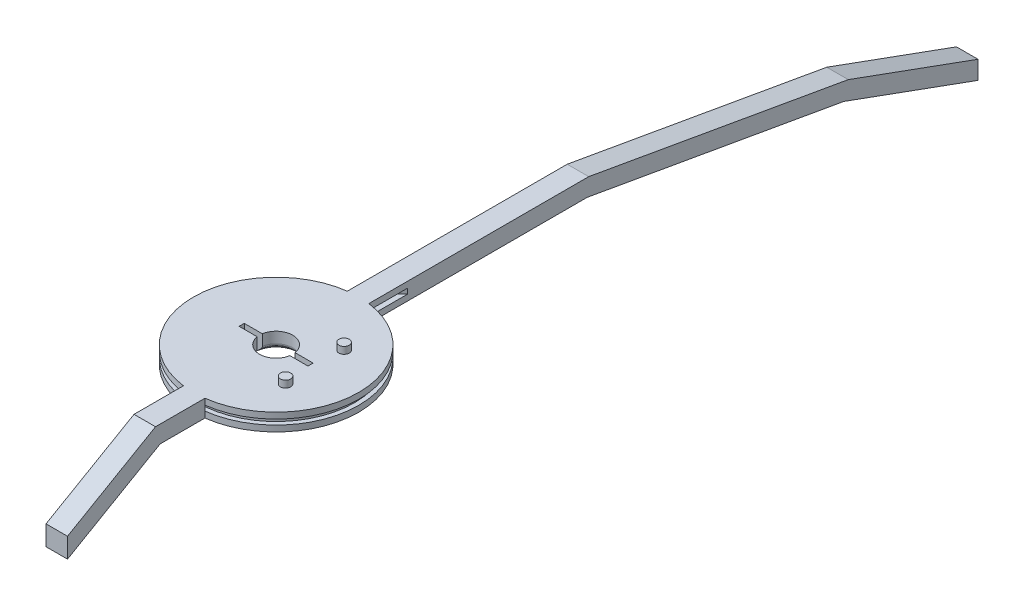
SolidWorks part; units mm, degrees
ref_plane "Front Plane" through (0, 0, 0) normal (0, 0, 1) x (1, 0, 0)
ref_plane "Top Plane" through (0, 0, 0) normal (0, 1, 0) x (1, 0, 0)
ref_plane "Right Plane" through (0, 0, 0) normal (1, 0, 0) x (0, 0, -1)
sketch "Sketch1" plane through (0, 0, 0) normal (0, 1, 0) x (1, 0, 0)
  circle A0 centre (0, 0) radius 9.1071
  dimension "D1" = 18.2143
extrude "MidSection" add sketch "Sketch1" along normal blind 0.6
ref_plane "Plane1" through (0, 0.3, 0) normal (0, 1, 0) x (1, 0, 0)
sketch "Sketch2" plane through (0, 0, 0) normal (1, 0, 0) x (0, 0, -1)
  line L0 (9.1071, 0.6) -> (-9.1071, 0.6) construction
  line L1 (9.1071, 0.6) -> (-9.1071, 0.6)
  line L2 (0, 0.6) -> (0, 1.3)
  line L3 (0, 1.3) -> (9.6071, 1.3)
  line L4 (9.6071, 1.3) -> (9.6071, 1)
  line L5 (9.6071, 1) -> (9.1071, 0.6)
  line L6 (0, 0.6) -> (0, 3.326) construction
  line L7 (9.1071, 0.6) -> (9.6071, 0.6)
  line L8 (9.6071, 0.6) -> (9.6071, 1)
  dimension "D1" = 0.7
  dimension "D2" = 0.5
  dimension "D3" = 0.3
revolve "Cap" add sketch "Sketch2" angle 360 about L6 region at (0, 0.9533, -4.7336) region at (0, 0.7333, -9.4405)
mirror "Cap2" about plane through (0, 0.3, 0) normal (0, 1, 0) of "Cap"
ref_plane "Plane2" through (9.1071, 0, 0) normal (1, 0, 0) x (0, 0, -1)
sketch "Sketch5" plane through (0, 1.3, 0) normal (0, 1, 0) x (1, 0, 0)
  line L3 (-8.4077, 3.5) -> (8.4077, 3.5) construction
  line L9 (0, 0) -> (-3.1386, 0) construction
  line L11 (-8.5633, 3.1) -> (8.4077, 3.1)
  line L15 (-8.2298, 3.9) -> (8.2298, 3.9)
  line L16 (-8.4077, 3.9) -> (8.4077, 3.9) construction
  line L17 (-8.4077, 3.1) -> (8.4077, 3.1) construction
  line L18 (8.4077, 3.1) -> (8.5633, 3.1)
  line L19 (8.4077, -3.1) -> (8.5633, -3.1)
  line L20 (-8.2298, -3.9) -> (8.2298, -3.9)
  line L21 (-8.5633, -3.1) -> (8.4077, -3.1)
  line L22 (-5.919, 3.1) -> (-5.919, 3.9)
  line L23 (-5.919, -3.1) -> (-5.919, -3.9)
  arc A2 (-5.919, 3.1) -> (-9.1049, 0.2) centre (-5.919, -0.1) ccw
  circle A3 centre (0, 0) radius 9.1071 construction
  arc A8 (-5.919, -3.1) -> (-9.1049, -0.2) centre (-5.919, 0.1) cw
  circle A14 centre (0, 0) radius 9.1071
  dimension "D1" = 3.2
  dimension "D4" = 0.4
  dimension "D2" = 0.2
  dimension "D3" = 3.5
  dimension "D5" = 0.4
extrude "CableSlots" cut sketch "Sketch5" against normal up to surface (1.3 mm away) from surface contours L15 A14 L11 L22 | L11 A14 A2 | A8 A14 L21 | L21 A14 L20 L23 region at (-7.1634, 1.3, -3.4911) region at (-8.2017, 1.3, -2.422) region at (-8.2017, 1.3, 2.422) region at (-7.1634, 1.3, 3.4911) up to face at (0, 0, 9.1071) starting at face at (0, 0.6, 9.1071)
sketch "Sketch6" plane through (0, 1.3, 0) normal (0, 1, 0) x (1, 0, 0)
  line L0 (-5.919, -3.1) -> (-5.919, -3.9) construction
  line L1 (-5.919, -3.1) -> (-5.919, -3.9) construction
  line L2 (0, 0) -> (2.8045, 0) construction
  circle A0 centre (4.5, -3.4) radius 1
  circle A1 centre (4.5, 3.4) radius 1
  circle A2 centre (4.5, 3.4) radius 0.6
  circle A13 centre (4.5, -3.4) radius 0.6
  dimension "D4" = 1.2
  dimension "D2" = 4.5
extrude "CablePresserBolt_Markers" add sketch "Sketch6" along normal offset from surface (0.8 mm away) 0.8 contours A2 | A13 region at (4.5, 1.3, -3.4) region at (4.5, 1.3, 3.4) up to face at (0, 1.3, -9.6071) offset beyond the face yes
sketch "Sketch8" plane through (0, 1.3, 0) normal (0, 1, 0) x (1, 0, 0)
  circle A0 centre (0, 0) radius 1.925
  dimension "D1" = 3.85
extrude "BallBearingSlot" cut sketch "Sketch8" against normal through all
sketch "Sketch15" plane through (0, 0, 0) normal (1, 0, 0) x (0, 0, -1)
  line L0 (-9.6071, -0.7) -> (9.6071, -0.7) construction
  line L1 (-9.6071, -0.7) -> (9.6071, -0.7) construction
  line L2 (0, -0.7) -> (2.5, -0.7)
  line L3 (1.925, 0.0307) -> (1.925, 1.8136) construction
  line L4 (2.5, -0.7) -> (2.1, -0.3)
  line L5 (1.925, 0.0307) -> (1.925, -0.7)
  arc A0 (1.925, 0.0307) -> (2.1, -0.3) centre (2.325, 0.0307) ccw
  dimension "D5" = 0.4
  dimension "D1" = 2.5
  dimension "D2" = 1.925
  dimension "D4" = 0.4
  dimension "D3" = 2.1
revolve "BearingInsertionSlope" cut sketch "Sketch15" angle 360 about axis through (0, 0.6, 0) along (0, -1, 0) region at (0, -0.5032, -2.1143)
sketch "Sketch16" plane through (0, -0.7, 0) normal (0, -1, 0) x (1, 0, 0)
  line L0 (0, 0) -> (4, 0) construction
  line L1 (0, -0.3) -> (4, -0.3)
  line L2 (0, 0.3) -> (4, 0.3)
  line L3 (0, -0.3) -> (0, 0.3)
  line L4 (4, -0.3) -> (4, 0.3)
  dimension "D1" = 4
  dimension "D2" = 0.3
  dimension "D3" = 0.3
extrude "DeformCut" cut sketch "Sketch16" against normal through all
pattern_circular "CirPattern1" count 2 over 360 about axis through (0, 1.3, 0) along (0, 1, 0) of "DeformCut"
sketch "Sketch17" plane through (0, 0, 0) normal (1, 0, 0) x (0, 0, -1)
  line L0 (0, 0.3) -> (35, 0.3) construction
  line L1 (35, 0.3) -> (65, -4.9898) construction
  line L2 (65, -4.9898) -> (80, -10.4494) construction
  line L3 (0, 0.3) -> (-15, 0.3) construction
  line L4 (-15, 0.3) -> (-25, -5.4735) construction
  line L5 (0, 1.3) -> (0, -0.7) construction
  line L6 (65.2598, -4.0202) -> (80.342, -9.5097)
  line L7 (35.0875, 1.3) -> (65.2598, -4.0202)
  line L8 (0, 1.3) -> (35.0875, 1.3)
  line L9 (0.3, -0.7) -> (0.3, 1.3)
  line L10 (-0.3, -0.7) -> (0.3, -0.7)
  line L11 (-0.3, 1.3) -> (-0.3, -0.7)
  line L12 (0.3, 1.3) -> (-0.3, 1.3)
  line L13 (0.3, -0.7) -> (0.3, 1.3) construction
  line L14 (-0.3, -0.7) -> (0.3, -0.7) construction
  line L15 (-0.3, 1.3) -> (-0.3, -0.7) construction
  line L16 (0.3, 1.3) -> (-0.3, 1.3) construction
  line L17 (0, 1.3) -> (-15.2679, 1.3)
  line L18 (-15.2679, 1.3) -> (-25.5, -4.6075)
  line L19 (64.7402, -5.9594) -> (79.658, -11.3891)
  line L20 (34.9125, -0.7) -> (64.7402, -5.9594)
  line L21 (0, -0.7) -> (34.9125, -0.7)
  line L22 (0, -0.7) -> (-14.7321, -0.7)
  line L23 (-14.7321, -0.7) -> (-24.5, -6.3395)
  line L24 (-25.5, -4.6075) -> (-25.5, -6.9169)
  line L25 (-25.5, -6.9169) -> (-24.5, -6.3395)
  line L28 (80.342, -9.5097) -> (80.342, -11.638)
  line L29 (80.342, -11.638) -> (79.658, -11.3891)
  line L30 (-9.6071, 1.3) -> (-9.6071, 0.6) construction
  line L31 (-9.6071, 1.3) -> (-9.6071, 0.6)
  line L32 (9.6071, 0.6) -> (9.6071, 1.3) construction
  line L33 (9.6071, 0.6) -> (9.6071, 1.3)
  line L34 (-9.6071, 0.6) -> (-9.6071, -0.7)
  line L35 (-9.6071, 0) -> (-9.6071, -0.7) construction
  line L36 (9.6071, 0.6) -> (9.6071, -0.7)
  line L37 (9.6071, -0.7) -> (9.6071, 0) construction
  dimension "D1" = 170
  dimension "D2" = 170
  dimension "D3" = 80
  dimension "D4" = 35
  dimension "D5" = 30
  dimension "D6" = 150
  dimension "D7" = 25
  dimension "D8" = 15
  dimension "D9" = 0
  dimension "D10" = 1
  dimension "D11" = 1
extrude "BossExtrude" add sketch "Sketch17" along normal mid plane 2.5 separate body contours L34 L31 L17 L18 L24 L25 L23 L22 | L33 L36 L21 L20 L19 L29 L28 L6 L7 L8 region at (0, -7.4406, -72.555) region at (0, -1.7992, 17.8035)
sketch "Sketch18" plane through (0, 0, -9.6071) normal (0, 0, 1) x (1, 0, 0)
  line L4 (-1.25, 1.3) -> (-1.25, -0.7)
  line L5 (-1.25, -0.7) -> (1.25, -0.7)
  line L6 (1.25, -0.7) -> (1.25, 1.3)
  line L7 (1.25, 1.3) -> (-1.25, 1.3)
  line L8 (-1.25, 1.3) -> (-1.25, -0.7)
  line L9 (-1.25, -0.7) -> (1.25, -0.7)
  line L10 (1.25, -0.7) -> (1.25, 1.3)
  line L11 (1.25, 1.3) -> (-1.25, 1.3)
  dimension "D1" = 0
extrude "Boss-Extrude3" add sketch "Sketch18" along normal up to surface (0.0817 mm away) up to face at (0, 0.6, -9.6071)
sketch "Sketch19" plane through (0, 0, 9.6071) normal (0, 0, -1) x (-1, 0, 0)
  line L4 (1.25, -0.7) -> (1.25, 1.3)
  line L5 (1.25, 1.3) -> (-1.25, 1.3)
  line L6 (-1.25, 1.3) -> (-1.25, -0.7)
  line L7 (-1.25, -0.7) -> (1.25, -0.7)
  line L8 (1.25, -0.7) -> (1.25, 1.3)
  line L9 (1.25, 1.3) -> (-1.25, 1.3)
  line L10 (-1.25, 1.3) -> (-1.25, -0.7)
  line L11 (-1.25, -0.7) -> (1.25, -0.7)
  dimension "D1" = 0
extrude "Boss-Extrude4" add sketch "Sketch19" along normal up to surface (0.0817 mm away) up to face at (0, 0.95, 0.0408)
sketch "Sketch14" plane through (0, 1.3, 0) normal (0, 1, 0) x (1, 0, 0)
  line L2 (-6.4072, 6.4721) -> (1.25, 14.0255)
  line L3 (-1.25, 9.5255) -> (-1.25, 35.0875) construction
  line L4 (1.25, 9.5255) -> (1.25, 35.0875) construction
  line L5 (-1.25, 9.5255) -> (-1.25, 35.0875)
  line L6 (1.25, 9.5255) -> (1.25, 35.0875)
  arc A2 (-8.2298, -3.9) -> (-8.2298, 3.9) centre (0, 0) ccw construction
  arc A3 (-8.2298, -3.9) -> (-8.2298, 3.9) centre (0, 0) ccw construction
  arc A8 (1.25, 9.5255) -> (-1.25, 9.5255) centre (0, 0) ccw
  arc A9 (-1.25, 9.5255) -> (-1.25, -9.5255) centre (0, 0) ccw
  arc A10 (-1.25, -9.5255) -> (1.25, -9.5255) centre (0, 0) ccw
  arc A11 (1.25, -9.5255) -> (1.25, 9.5255) centre (0, 0) ccw
  arc A12 (1.25, 9.5255) -> (-1.25, 9.5255) centre (0, 0) ccw
  arc A13 (-1.25, 9.5255) -> (-1.25, -9.5255) centre (0, 0) ccw
  arc A14 (-1.25, -9.5255) -> (1.25, -9.5255) centre (0, 0) ccw
  arc A15 (1.25, -9.5255) -> (1.25, 9.5255) centre (0, 0) ccw
  line M41 (1.25, 9.5255) -> (1.25, 35.0875)
  line M43 (-1.25, 35.0875) -> (-1.25, 9.5255)
  dimension "D1" = 4.5
  dimension "D2" = 0
extrude "CableClearanceCut" cut sketch "Sketch14" against normal up to surface (1.3 mm away) from surface contours A12 L2 M41 M43 region at (0.1599, 1.3, -11.265) up to face at (-5.2666, 0, 0) starting at face at (-5.2666, 0.6, 0)
equation "\"BoltD\"=2mm"
equation "\"SmallScrewD\"=1.2mm"
equation "\"SmallScrewHatD\"=2mm"
equation "\"TubeOuterD\"=1.2mm"
equation "\"BasicPulleyD\"=15mm"
equation "\"GrooveDepth\"=0.7mm"
equation "\"Cable1D\"=0.4mm"
equation "\"Cable2D\"=0.3mm"
equation "\"BallBearingInnerD\"=2mm"
equation "\"BallBearingOuterD\"=4mm"
equation "\"D1@Sketch1\" = \"PulleyD\""
equation "\"D1@MidSection\"=\"Cable2D\" * 2"
equation "\"D4@Sketch6\"=\"SmallScrewD\""
equation "\"D1@Sketch8\"=\"BallBearingOuterD\"-0.15"
equation "\"BoltHatD\"=3.2mm"
equation "\"BallBearingThickness\"=2mm"
equation "\"HumerusL\"=37.2mm"
equation "\"HumerusElbowSidePulleyD\"=10mm"
equation "\"RadiusL\"=68.1mm"
equation "\"Finger1L\"=120mm"
equation "\"Finger2L\"=100mm"
equation "\"Finger3L\"=80mm"
equation "\"ElbowExtendedAngle\"=140deg"
equation "\"ElbowFlexedAngle\"=38deg"
equation "\"PulleyD\"= \"HumerusElbowSidePulleyD\" * ( \"ElbowExtendedAngle\" - \"ElbowFlexedAngle\" ) / ( \"Digit5ExtendedAngle\" - \"Digit5FlexedAngle\" )"
equation "\"D1@Sketch15\"=\"BallBearingOuterD\"/2+0.5"
equation "\"D2@Sketch15\"=\"BallBearingOuterD\"/2 - 0.075"
equation "\"BearingCapD\"=12mm"
equation "\"TubeClipW\"=1.5mm"
equation "\"TubeClipH\"=1.5mm"
equation "\"TubeClipLock_SideL\"=1.5mm"
equation "\"TubeClipLock_W\"=0.7mm"
equation "\"Digit5ExtendedAngle\"=80deg"
equation "\"Digit5FlexedAngle\"=24deg"
equation "\"Digit4ExtendedAngle\"=108deg"
equation "\"Digit4FlexedAngle\"=34deg"
equation "\"Digit3ExtendedAngle\"=145deg"
equation "\"Digit3FlexedAngle\"=44deg"
equation "\"XL330_M077_T_FrameBoltD\"=1.6mm"
equation "\"KST_ServoShaftBoltD\"=2.5mm"
equation "\"KST_ServoShaftBoltHatD\"=5.2mm"
equation "\"D1@Sketch6\"=\"Cable2D\""
equation "\"NutD\"=3.9mm"
equation "\"XL330_M077_T_FrameBoltHatD\"=2.9mm"
equation "\"XL330_M077_T_FrameNutD\"=2.5mm"
equation "\"XL330_M077_T_HornScrewD\"=1.9mm"
equation "\"XL330_M077_T_HornScrewHatD\"=3.3mm"
